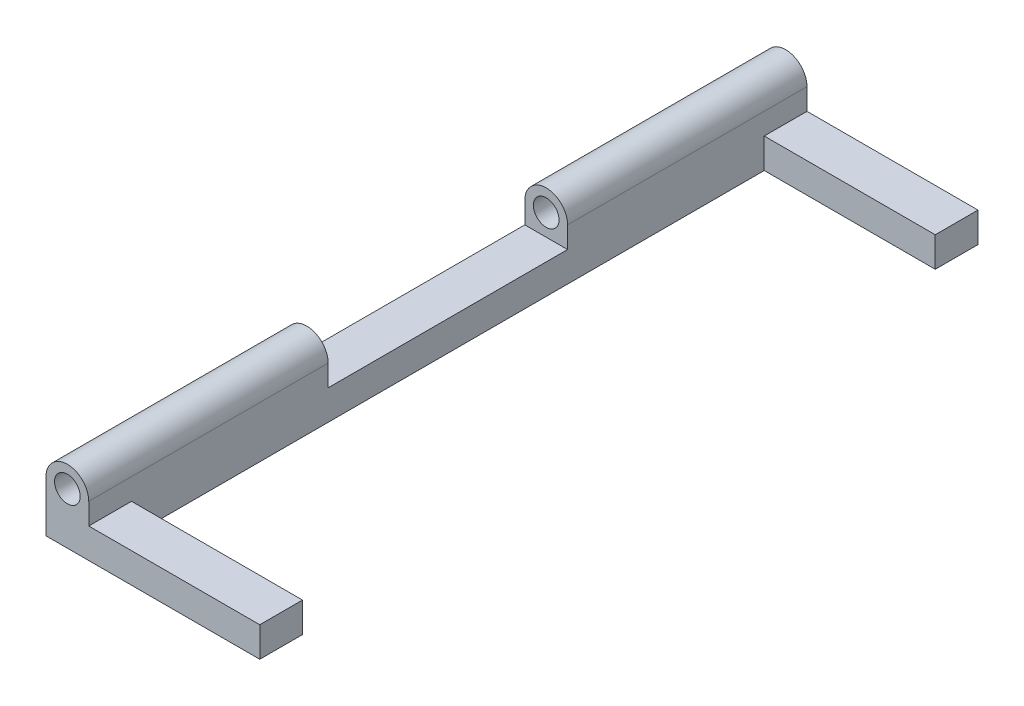
SolidWorks part; units mm, degrees
ref_plane "Front Plane" through (0, 0, 0) normal (0, 0, 1) x (1, 0, 0)
ref_plane "Top Plane" through (0, 0, 0) normal (0, 1, 0) x (1, 0, 0)
ref_plane "Right Plane" through (0, 0, 0) normal (1, 0, 0) x (0, 0, -1)
sketch "Sketch1" plane through (0, 0, 0) normal (0, 0, 1) x (1, 0, 0)
  line L0 (-1.25, -0.1288) -> (-1.25, -3.1288)
  line L1 (-1.25, -3.1288) -> (1.25, -3.1288)
  line L2 (1.25, -3.1288) -> (1.25, -0.1288)
  circle A0 centre (0, -0.1288) radius 0.75
  arc A1 (-1.25, -0.1288) -> (1.25, -0.1288) centre (0, -0.1288) cw
  point P7 (0, -3.1288)
  point P9 (0, 0)
  dimension "D1" = 1.5
  dimension "D2" = 2.5
  dimension "D3" = 3
extrude "Boss-Extrude1" add sketch "Sketch1" along normal blind 42
sketch "Sketch2" plane through (0, 0, 0) normal (1, 0, 0) x (0, 0, -1)
  line L0 (0, 1.1212) -> (-42, 1.1212) construction
  line L1 (-14, 1.1212) -> (-28, 1.1212)
  line L2 (-14, 1.1212) -> (-14, -1.3788)
  line L3 (-14, -1.3788) -> (-28, -1.3788)
  line L4 (-28, 1.1212) -> (-28, -1.3788)
  line L5 (-42, 1.1212) -> (0, 1.1212) construction
  point P6 (-21, 1.1212)
  point P11 (-21, 1.1212)
  dimension "D1" = 14
  dimension "D2" = 2.5
extrude "Cut-Extrude1" cut sketch "Sketch2" against normal through all both and the other way through all
sketch "Sketch3" plane through (1.25, 0, 0) normal (1, 0, 0) x (0, 0, -1)
  line L1 (-42, -3.1288) -> (-39.5, -3.1288)
  line L2 (-42, -3.1288) -> (-42, -1.3788)
  line L3 (-42, -1.3788) -> (-39.5, -1.3788)
  line L4 (-39.5, -3.1288) -> (-39.5, -1.3788)
  line L5 (0, -3.1288) -> (-2.5, -3.1288)
  line L6 (0, -3.1288) -> (0, -1.3788)
  line L7 (0, -1.3788) -> (-2.5, -1.3788)
  line L8 (-2.5, -3.1288) -> (-2.5, -1.3788)
  line L9 (-28, -1.3788) -> (-14, -1.3788) construction
  dimension "D1" = 2.5
extrude "Boss-Extrude2" add sketch "Sketch3" along normal blind 10
